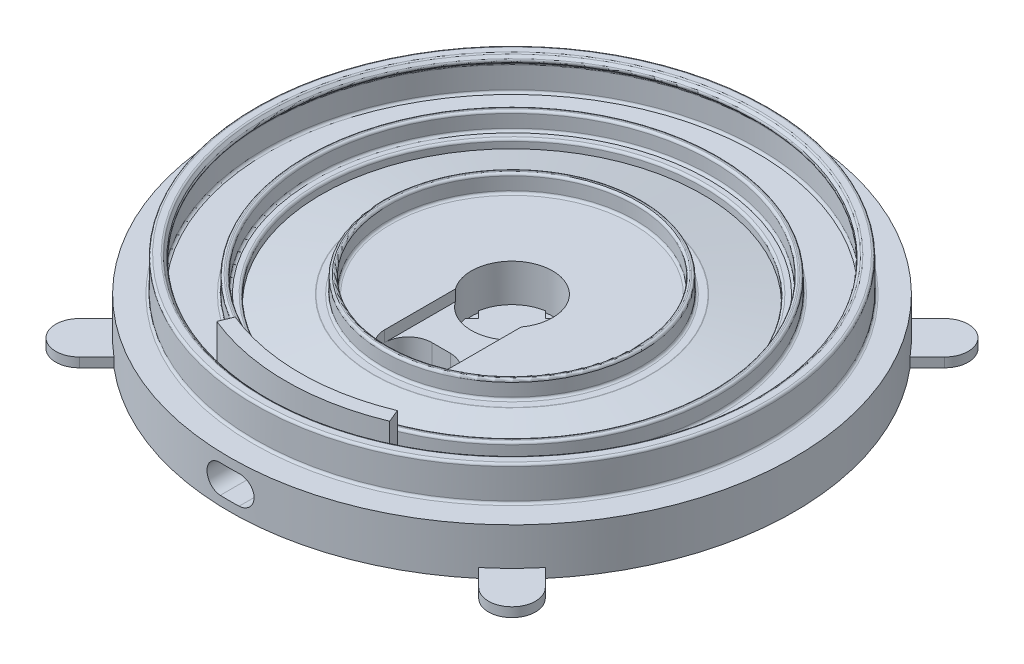
SolidWorks part; units mm, degrees
material "PLA"
ref_plane "Front Plane" through (0, 0, 0) normal (0, 0, 1) x (1, 0, 0)
ref_plane "Top Plane" through (0, 0, 0) normal (0, 1, 0) x (1, 0, 0)
ref_plane "Right Plane" through (0, 0, 0) normal (1, 0, 0) x (0, 0, -1)
sketch "Sketch1" plane through (0, 0, 0) normal (0, 1, 0) x (1, 0, 0)
  circle A0 centre (0, 0) radius 60
  circle A1 centre (0, 0) radius 40
  circle A2 centre (0, 0) radius 30
  dimension "D1" = 60
  dimension "D2" = 80
  dimension "D3" = 120
extrude "Boss-Extrude1" add sketch "Sketch1" along normal blind 10 contours A0
sketch "Sketch2" plane through (0, 0, 0) normal (0, 0, 1) x (1, 0, 0)
  line L0 (0, 10) -> (-29.5, 10)
  line L1 (60, 10) -> (-60, 10) construction
  line L2 (-29.5, 10) -> (-40.5, 8.127)
  line L3 (-40.5, 8.127) -> (-40.5, 10)
  line L4 (-40.5, 10) -> (-29.5, 10)
  line L5 (0, 10) -> (0, 0) construction
  dimension "D1" = 11
  dimension "D2" = 29.5
  dimension "D3" = 1.873
revolve "Cut-Revolve1" cut sketch "Sketch2" angle 360 about L5
sketch "Sketch3" plane through (0, 10, 0) normal (0, 1, 0) x (1, 0, 0)
  circle A0 centre (0, 0) radius 27.5
  circle A1 centre (0, 0) radius 26.25
  circle A2 centre (0, 0) radius 42.5
  circle A3 centre (0, 0) radius 43.75
  dimension "D1" = 55
  dimension "D2" = 52.5
  dimension "D3" = 85
  dimension "D4" = 87.5
extrude "Boss-Extrude2" add sketch "Sketch3" along normal blind 3.723 contours A1 | A0 | A2 | A3
fillet "Fillet1" radius 0.5 10 edges at (0, 10, 26.25) (0, 10, 27.5) (0, 10, 43.75) (0, 10, 42.5) (0, 10, 40.5) (0, 13.723, 27.5) (0, 13.723, 26.25) (0, 13.723, 43.75) (0, 13.723, 42.5) (0, 10, 29.5)
sketch "Sketch5" plane through (0, 0, 0) normal (0, 0, 1) x (1, 0, 0)
  line L0 (0, 10) -> (-52.5, 10) construction
  line L1 (60, 10) -> (-60, 10) construction
  line L2 (-52.5, 10) -> (-54.5, 10)
  line L3 (-54.5, 10) -> (-54.5, 17.323)
  line L4 (-54.5, 17.323) -> (-52.5, 17.323)
  line L5 (-52.5, 17.323) -> (-51.5, 16.323)
  line L6 (-51.5, 16.323) -> (-52.5, 15.323)
  line L7 (-52.5, 15.323) -> (-52.5, 10)
  line L8 (0, 10) -> (0, 24.5479) construction
  line L9 (0, -7.5476) -> (0, 7.5476) construction
  dimension "D1" = 52.5
  dimension "D2" = 7.323
  dimension "D3" = 1
  dimension "D4" = 1
  dimension "D5" = 2
  dimension "D6" = 2
revolve "Revolve1" add sketch "Sketch5" angle 360 about L8
fillet "Fillet2" radius 0.5 6 edges at (0, 10, -52.5) (0, 15.323, -52.5) (0, 17.323, -52.5) (0, 16.323, -51.5) (0, 10, -54.5) (0, 17.323, -54.5)
sketch "Sketch6" plane through (0, 10, 0) normal (0, 1, 0) x (1, 0, 0)
  circle A0 centre (0, 0) radius 8.625
  dimension "D1" = 17.25
extrude "Cut-Extrude1" cut sketch "Sketch6" against normal blind 8.354
sketch "Sketch9" plane through (0, 10, 0) normal (0, 1, 0) x (1, 0, 0)
  line L1 (-7, -5.0389) -> (7, -5.0389)
  line L2 (-7, -5.0389) -> (-7, -20.0389)
  line L3 (-7, -20.0389) -> (7, -20.0389)
  line L4 (7, -5.0389) -> (7, -20.0389)
  circle A0 centre (0, 0) radius 8.625 construction
  circle A1 centre (0, 0) radius 8.625 construction
  dimension "D1" = 15
  dimension "D2" = 14
extrude "Cut-Extrude2" cut sketch "Sketch9" against normal blind 2.354
sketch "Sketch10" plane through (0, 10, 0) normal (0, 1, 0) x (1, 0, 0)
  line L0 (2, -20.0389) -> (-2, -20.0389) construction
  line L1 (-7, -20.0389) -> (7, -20.0389) construction
  line L2 (2, -25.0389) -> (-2, -25.0389)
  line L3 (2, -15.0389) -> (-2, -15.0389)
  arc A0 (2, -25.0389) -> (2, -15.0389) centre (2, -20.0389) ccw
  arc A1 (-2, -15.0389) -> (-2, -25.0389) centre (-2, -20.0389) ccw
  point P4 (0, -20.0389)
  dimension "D1" = 5
extrude "Cut-Extrude3" cut sketch "Sketch10" against normal blind 10
sketch "Sketch11" plane through (0, 0, 25.0389) normal (0, 0, -1) x (-1, 0, 0)
  line L0 (-2, 5) -> (2, 5) construction
  line L1 (-2, 8) -> (2, 8)
  line L2 (-2, 2) -> (2, 2)
  line L3 (2, 0) -> (2, 10) construction
  line L4 (-2, 0) -> (-2, 10) construction
  line L5 (2, 0) -> (-2, 0) construction
  arc A0 (-2, 8) -> (-2, 2) centre (-2, 5) ccw
  arc A1 (2, 2) -> (2, 8) centre (2, 5) ccw
  point P2 (0, 5)
  dimension "D1" = 3
  dimension "D2" = 2
extrude "Cut-Extrude4" cut sketch "Sketch11" against normal blind 40 and the other way blind 2
sketch "Sketch12" plane through (0, 0, 0) normal (0, -1, 0) x (1, 0, 0)
  line L0 (-45.9619, -45.9619) -> (45.9619, 45.9619) construction
  line L1 (-49.4975, -42.4264) -> (42.4264, 49.4975)
  line L2 (-42.4264, -49.4975) -> (49.4975, 42.4264)
  line L3 (9.5276, 0) -> (-9.5276, 0) construction
  line L4 (45.9619, -45.9619) -> (-45.9619, 45.9619) construction
  line L5 (42.4264, -49.4975) -> (-49.4975, 42.4264)
  line L6 (49.4975, -42.4264) -> (-42.4264, 49.4975)
  line L7 (0, -9.5276) -> (0, 9.5276) construction
  arc A0 (-49.4975, -42.4264) -> (-42.4264, -49.4975) centre (-45.9619, -45.9619) ccw
  arc A1 (49.4975, 42.4264) -> (42.4264, 49.4975) centre (45.9619, 45.9619) ccw
  circle A2 centre (0, 0) radius 60 construction
  arc A3 (42.4264, -49.4975) -> (49.4975, -42.4264) centre (45.9619, -45.9619) ccw
  arc A4 (-42.4264, 49.4975) -> (-49.4975, 42.4264) centre (-45.9619, 45.9619) ccw
  point P2 (0, 0)
  point P14 (0, 0)
  dimension "D2" = 5
  dimension "D4" = 5
  dimension "D1" = 65
  dimension "D3" = 45
  dimension "D5" = 65
  dimension "D6" = 45
extrude "Boss-Extrude3" add sketch "Sketch12" against normal blind 2 contours L6 A4 L5 A3 | L2 A1 L1 A0
sketch "Sketch13" plane through (0, 10, 0) normal (0, 1, 0) x (1, 0, 0)
  line L0 (-18.3688, -44.3462) -> (-17.2208, -41.5746)
  line L1 (-17.2208, -41.5746) -> (0, 0) construction
  line L2 (0, 0) -> (17.2208, -41.5746) construction
  line L3 (17.2208, -41.5746) -> (18.3688, -44.3462)
  line L4 (0, -9.5276) -> (0, 9.5276) construction
  arc A0 (-17.2208, -41.5746) -> (17.2208, -41.5746) centre (0, 0) ccw
  arc A1 (-18.3688, -44.3462) -> (18.3688, -44.3462) centre (0, 0) ccw
  point P6 (0, -48)
  dimension "D1" = 45
  dimension "D2" = 48
  dimension "D3" = 45
  dimension "D4" = 45
extrude "Boss-Extrude4" add sketch "Sketch13" along normal blind 8
